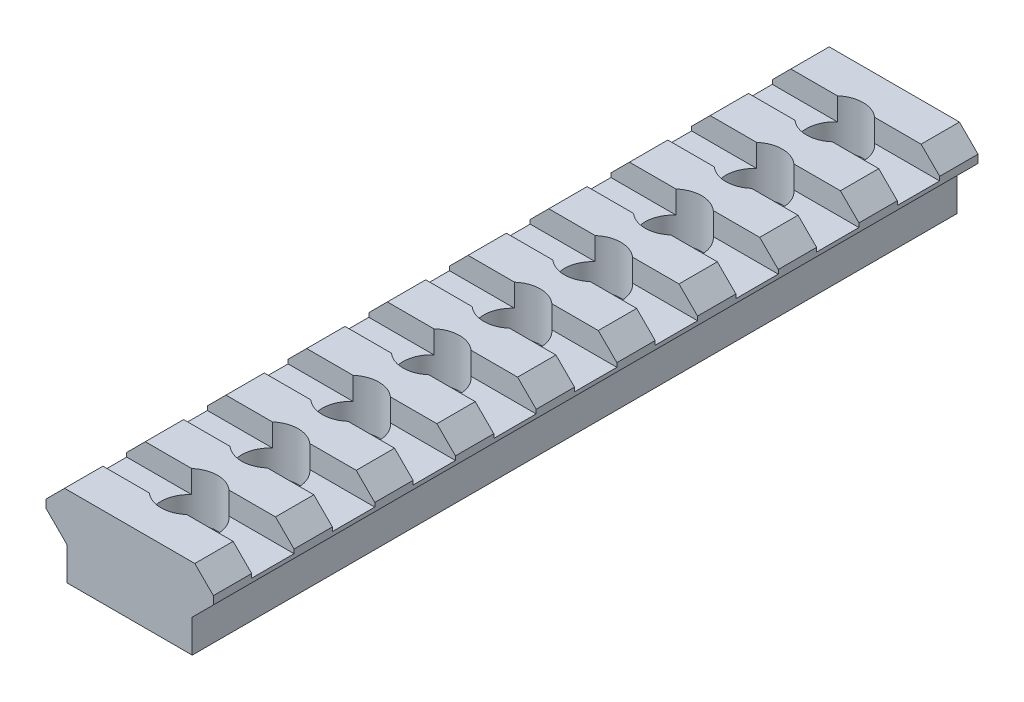
SolidWorks part; units mm, degrees
ref_plane "Płaszczyzna przednia" through (0, 0, 0) normal (0, 0, 1) x (1, 0, 0)
ref_plane "Płaszczyzna górna" through (0, 0, 0) normal (0, 1, 0) x (1, 0, 0)
ref_plane "Płaszczyzna prawa" through (0, 0, 0) normal (1, 0, 0) x (0, 0, -1)
sketch "Szkic1" plane through (0, 0, 0) normal (0, 0, 1) x (1, 0, 0)
  line L0 (2.8, 2.8) -> (0, 0)
  line L5 (3.12, -3.12) -> (18.62, -3.12) construction
  line L6 (1.37, 1.37) -> (20.37, 1.37) construction
  line L7 (0, 0) -> (3.12, -3.12)
  line L8 (18.94, 2.8) -> (21.74, 0)
  line L9 (21.74, 0) -> (18.62, -3.12)
  line L14 (2.8, 2.8) -> (18.94, 2.8)
  line L15 (21.74, 0) -> (0, 0) construction
  line L16 (1.37, 1.37) -> (1.37, -1.37) construction
  line L17 (1.37, -1.37) -> (20.37, -1.37) construction
  line L18 (20.37, 1.37) -> (20.37, -1.37) construction
  line L24 (3.12, -3.12) -> (3.12, -7.2)
  line L25 (3.12, -7.2) -> (18.62, -7.2)
  line L26 (18.62, -7.2) -> (18.62, -3.12)
  dimension "D1" = 19
  dimension "D2" = 45
  dimension "D3" = 15.5
  dimension "D4" = 10
  dimension "D5" = 4.17
  dimension "D6" = 2.74
extrude "Dodanie-wyciągnięcie2" add sketch "Szkic1" along normal blind 94.75
sketch "Szkic2" plane through (0, 2.8, 0) normal (0, 1, 0) x (1, 0, 0)
  line L0 (0, -14.75) -> (0, -20)
  line L6 (0, -94.75) -> (0, 0) construction
  line L7 (0, -4.75) -> (21.74, -4.75)
  line L8 (0, -4.75) -> (0, -10)
  line L9 (0, -10) -> (21.74, -10)
  line L10 (21.74, -4.75) -> (21.74, -10)
  line L11 (21.74, -94.75) -> (21.74, 0) construction
  line L12 (0, -14.75) -> (21.74, -14.75)
  line L14 (21.74, -14.75) -> (21.74, -20)
  line L24 (0, -20) -> (21.74, -20)
  line L26 (0, -24.75) -> (0, -30)
  line L28 (0, -24.75) -> (21.74, -24.75)
  line L30 (21.74, -24.75) -> (21.74, -30)
  line L32 (0, -30) -> (21.74, -30)
  line L34 (0, -34.75) -> (0, -40)
  line L35 (0, -34.75) -> (21.74, -34.75)
  line L60 (21.74, -34.75) -> (21.74, -40)
  line L61 (0, -40) -> (21.74, -40)
  line L62 (0, -44.75) -> (0, -50)
  line L63 (0, -44.75) -> (21.74, -44.75)
  line L64 (21.74, -44.75) -> (21.74, -50)
  line L65 (0, -50) -> (21.74, -50)
  line L66 (0, -54.75) -> (0, -60)
  line L67 (0, -54.75) -> (21.74, -54.75)
  line L68 (21.74, -54.75) -> (21.74, -60)
  line L69 (0, -60) -> (21.74, -60)
  line L70 (0, -64.75) -> (0, -70)
  line L71 (0, -64.75) -> (21.74, -64.75)
  line L72 (21.74, -64.75) -> (21.74, -70)
  line L73 (0, -70) -> (21.74, -70)
  line L74 (0, -74.75) -> (0, -80)
  line L75 (0, -74.75) -> (21.74, -74.75)
  line L76 (21.74, -74.75) -> (21.74, -80)
  line L77 (0, -80) -> (21.74, -80)
  line L78 (0, -84.75) -> (0, -90)
  line L79 (0, -84.75) -> (21.74, -84.75)
  line L80 (21.74, -84.75) -> (21.74, -90)
  line L81 (0, -90) -> (21.74, -90)
  dimension "D1" = 4.75
  dimension "D2" = 5.25
  dimension "D3" = 9
  dimension "D4" = 10
extrude "Wytnij-wyciągnięcie2" cut sketch "Szkic2" against normal blind 2.8
sketch "Szkic3" plane through (0, 0, 0) normal (0, 1, 0) x (1, 0, 0)
  line L0 (10.87, -7.375) -> (10.87, 0) construction
  line L1 (18.94, 0) -> (2.8, 0) construction
  line L2 (21.74, -7.375) -> (10.87, -7.375) construction
  line L3 (21.74, -10) -> (21.74, -4.75) construction
  circle A0 centre (10.87, -7.375) radius 1.75
  circle A9 centre (10.87, -17.375) radius 1.75
  circle A10 centre (10.87, -27.375) radius 1.75
  circle A11 centre (10.87, -37.375) radius 1.75
  circle A12 centre (10.87, -47.375) radius 1.75
  circle A13 centre (10.87, -57.375) radius 1.75
  circle A14 centre (10.87, -67.375) radius 1.75
  circle A15 centre (10.87, -77.375) radius 1.75
  circle A16 centre (10.87, -87.375) radius 1.75
  point P23 (10.87, 0)
  dimension "D2" = 3.5
  dimension "D4" = 10
  dimension "D3" = 9
other "Wyrównaj grupę1"
extrude "Wytnij-wyciągnięcie3" cut sketch "Szkic3" against normal through all
sketch "Szkic4" plane through (0, 0, -1.86) normal (0, -1, 0) x (1, 0, 0)
  circle A0 centre (10.87, 89.235) radius 3.5
  circle A9 centre (10.87, 89.235) radius 1.75 construction
  circle A10 centre (10.87, 79.235) radius 3.5
  circle A11 centre (10.87, 69.235) radius 3.5
  circle A12 centre (10.87, 59.235) radius 3.5
  circle A13 centre (10.87, 49.235) radius 3.5
  circle A14 centre (10.87, 39.235) radius 3.5
  circle A15 centre (10.87, 29.235) radius 3.5
  circle A16 centre (10.87, 19.235) radius 3.5
  circle A17 centre (10.87, 9.235) radius 3.5
  dimension "D1" = 7
  dimension "D2" = 9
extrude "Wytnij-wyciągnięcie4" cut sketch "Szkic4" along normal blind 3.2 and the other way through all
sketch "Sketch1" plane through (0, 0, 94.75) normal (0, 0, 1) x (1, 0, 0)
  line L0 (10.87, -7.2) -> (10.87, 10.5404) construction
  line L1 (0.5, 0.5) -> (0.5, -0.5)
  line L3 (3.12, -7.2) -> (18.62, -7.2) construction
  line L8 (18.94, 2.8) -> (2.8, 2.8)
  line L9 (2.8, 2.8) -> (0, 0)
  line L10 (0, 0) -> (3.12, -3.12)
  line L11 (3.12, -3.12) -> (3.12, -7.2)
  line L12 (3.12, -7.2) -> (18.62, -7.2)
  line L14 (18.62, -3.12) -> (21.74, 0)
  line L15 (21.74, 0) -> (18.94, 2.8)
  line L17 (0.5, 0.5) -> (0, 0)
  line L18 (0, 0) -> (0.5, -0.5)
  line L26 (21.74, 0) -> (21.24, -0.5)
  line L27 (21.24, 0.5) -> (21.74, 0)
  line L28 (21.24, 0.5) -> (21.24, -0.5)
  line L32 (18.62, -7.2) -> (18.62, -3.12)
  point P17 (0, 0)
  dimension "D1" = 0
extrude "Cut-Extrude1" cut sketch "Sketch1" against normal through all
